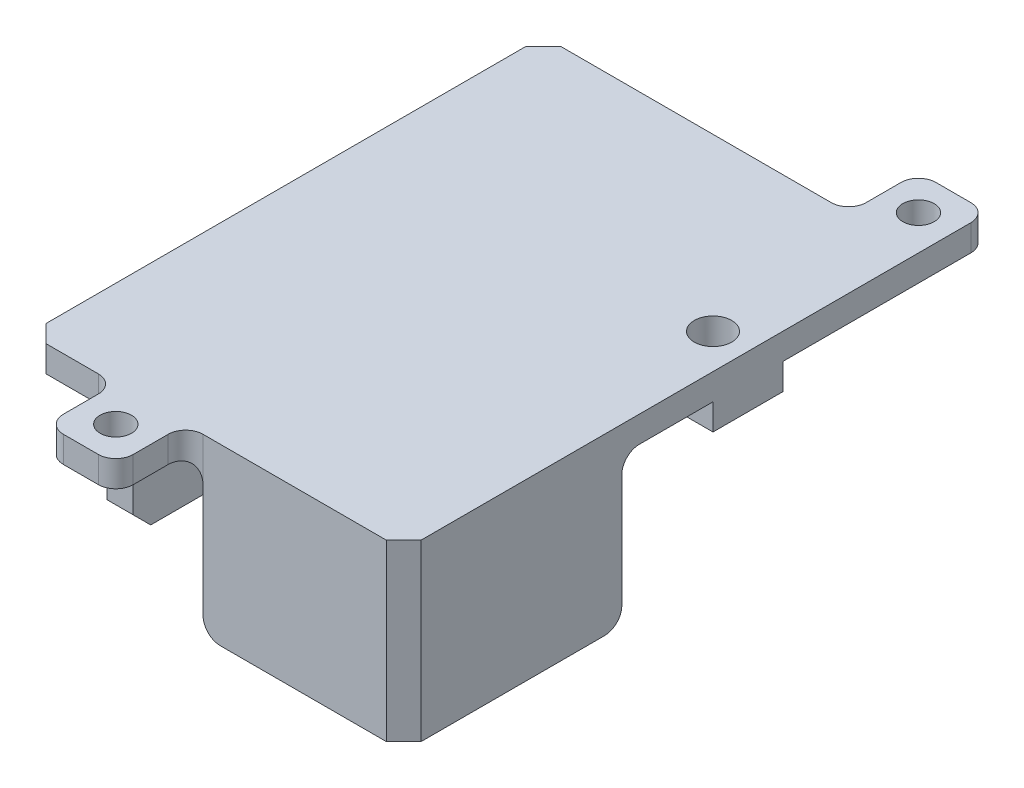
SolidWorks part; units mm, degrees
ref_plane "Płaszczyzna przednia" through (0, 0, 0) normal (0, 0, 1) x (1, 0, 0)
ref_plane "Płaszczyzna górna" through (0, 0, 0) normal (0, 1, 0) x (1, 0, 0)
ref_plane "Płaszczyzna prawa" through (0, 0, 0) normal (1, 0, 0) x (0, 0, -1)
sketch "Sketch1" plane through (0, 0, 0) normal (0, 1, 0) x (1, 0, 0)
  line L1 (0, 0) -> (43, 0)
  line L2 (0, 0) -> (0, 59)
  line L3 (0, 59) -> (43, 59)
  line L4 (43, 0) -> (43, 59)
  dimension "D1" = 59
  dimension "D2" = 43
extrude "Boss-Extrude1" add sketch "Sketch1" along normal blind 3
chamfer "Chamfer1" distance 2 angle 45 2 edges at (0, 1.5, 0) (0, 1.5, -59)
sketch "Sketch2" plane through (0, 0, 0) normal (-1, 0, 0) x (0, 0, 1)
  line L0 (-57, 3) -> (-2, 3) construction
  line L1 (-50, 3) -> (-31, 3)
  line L2 (-50, 3) -> (-50, -3)
  line L3 (-50, -3) -> (-31, -3)
  line L4 (-31, 3) -> (-31, -3)
  line L5 (-59, 0) -> (-59, 3) construction
  line L6 (0, 3) -> (0, 0) construction
  line L7 (-22.5, 3) -> (-9, 3)
  line L8 (-22.5, 3) -> (-22.5, -20)
  line L9 (-22.5, -20) -> (-9, -20)
  line L10 (-9, 3) -> (-9, -20)
  dimension "D1" = 9
  dimension "D2" = 19
  dimension "D3" = 6
  dimension "D4" = 9
  dimension "D5" = 13.5
  dimension "D6" = 23
extrude "Boss-Extrude2" add sketch "Sketch2" against normal blind 3
chamfer "Chamfer2" distance 2 angle 45 4 edges at (1.5, -20, -9) (1.5, -20, -22.5) (1.5, -3, -31) (1.5, -3, -50)
fillet "Fillet1" radius 2 4 edges at (1.5, 0, -50) (1.5, 0, -31) (1.5, 0, -9) (1.5, 0, -22.5)
sketch "Sketch3" plane through (0, 3, 0) normal (0, 1, 0) x (1, 0, 0)
  line L0 (43, 59) -> (2, 59) construction
  line L1 (35, 67) -> (43, 67)
  line L2 (35, 67) -> (35, 59)
  line L3 (35, 59) -> (43, 59)
  line L4 (43, 67) -> (43, 59)
  line L5 (35, 67) -> (43, 59) construction
  line L6 (35, 59) -> (43, 67) construction
  line L7 (43, 65) -> (43, 57) construction
  line L8 (35, 65) -> (35, 61) construction
  line L9 (2, 0) -> (43, 0) construction
  line L10 (10, -8) -> (18, -8)
  line L11 (10, -8) -> (10, 0)
  line L12 (10, 0) -> (18, 0)
  line L13 (18, -8) -> (18, 0)
  line L14 (10, -8) -> (18, 0) construction
  line L15 (10, 0) -> (18, -8) construction
  line L16 (18, 2) -> (18, -6) construction
  line L17 (10, -2) -> (10, -6) construction
  circle A0 centre (39, 63) radius 1.8
  circle A1 centre (14, -4) radius 1.8
  point P0 (39, 63)
  point P13 (14, -4)
  dimension "D1" = 3.6
  dimension "D2" = 3.6
extrude "Boss-Extrude3" add sketch "Sketch3" against normal up to surface (3 mm away) up to face at (7.2857, 0, -28.7143)
fillet "Fillet2" radius 2 7 edges at (18, 1.5, 0) (18, 1.5, 8) (10, 1.5, 0) (10, 1.5, 8) (35, 1.5, -59) (35, 1.5, -67) (43, 1.5, -67)
sketch "Sketch4" plane through (0, 0, 0) normal (0, 0, 1) x (1, 0, 0)
  line L0 (43, 3) -> (43, 0) construction
  line L1 (20, 3) -> (43, 3)
  line L2 (20, 3) -> (20, -17)
  line L3 (20, -17) -> (43, -17)
  line L4 (43, 3) -> (43, -17)
  dimension "D1" = 20
extrude "Boss-Extrude4" add sketch "Sketch4" against normal blind 3
sketch "Sketch5" plane through (43, 0, 0) normal (1, 0, 0) x (0, 0, -1)
  line L0 (3, -17) -> (0, -17) construction
  line L1 (0, 3) -> (25, 3)
  line L2 (0, 3) -> (0, -17)
  line L3 (0, -17) -> (25, -17)
  line L4 (25, 3) -> (25, -17)
  dimension "D1" = 25
extrude "Boss-Extrude5" add sketch "Sketch5" against normal blind 3
chamfer "Chamfer3" distance 2 angle 45 2 edges at (40, -8.5, -3) (43, -7, 0)
fillet "Fillet4" radius 2 4 edges at (20, 0, -1.5) (41.5, 0, -25) (41.5, -17, -25) (20, -17, -1.5)
sketch "Sketch6" plane through (0, 3, 0) normal (0, 1, 0) x (1, 0, 0)
  line L8 (35, 35.45) -> (43, 35.45)
  line L9 (35, 35.45) -> (35, 43.45)
  line L10 (35, 43.45) -> (43, 43.45)
  line L11 (43, 35.45) -> (43, 43.45)
  line L12 (35, 35.45) -> (43, 43.45) construction
  line L13 (35, 43.45) -> (43, 35.45) construction
  line L14 (43, 2) -> (43, 65) construction
  line L15 (33, 59) -> (2, 59) construction
  circle A0 centre (39, 39.45) radius 2.15
  point P0 (39, 39.45)
  point P11 (0, 0)
  dimension "D2" = 4.3
  dimension "D1" = 8
  dimension "D3" = 15.55
extrude "Boss-Extrude6" add sketch "Sketch6" against normal blind 6
fillet "Fillet5" radius 2 2 edges at (35, -1.5, -43.45) (35, -1.5, -35.45)
hole_wizard "Ø4.3 (4.3) Diameter Hole1" positions "Sketch7" profile "Sketch8" hole size "Ø4.3" standard "DIN" end condition through all
sketch "Sketch7" plane through (0, -3, 0) normal (0, -1, 0) x (-1, 0, 0)
  point P0 (-39, 39.45)
sketch "Sketch8" plane through (39, -3, -39.45) normal (1, 0, 0) x (0, 0, -1)
  line L0 (0, 0) -> (0, 6)
  line L1 (0, 6) -> (2.15, 6)
  line L2 (2.15, 6) -> (2.15, 0)
  line L5 (2.15, 0) -> (0, 0)
  line L11 (0, -6.35) -> (0, 107.95) construction
  dimension "Thru Hole Dia." = 4.3
  dimension "Thru Hole Depth" = 6
